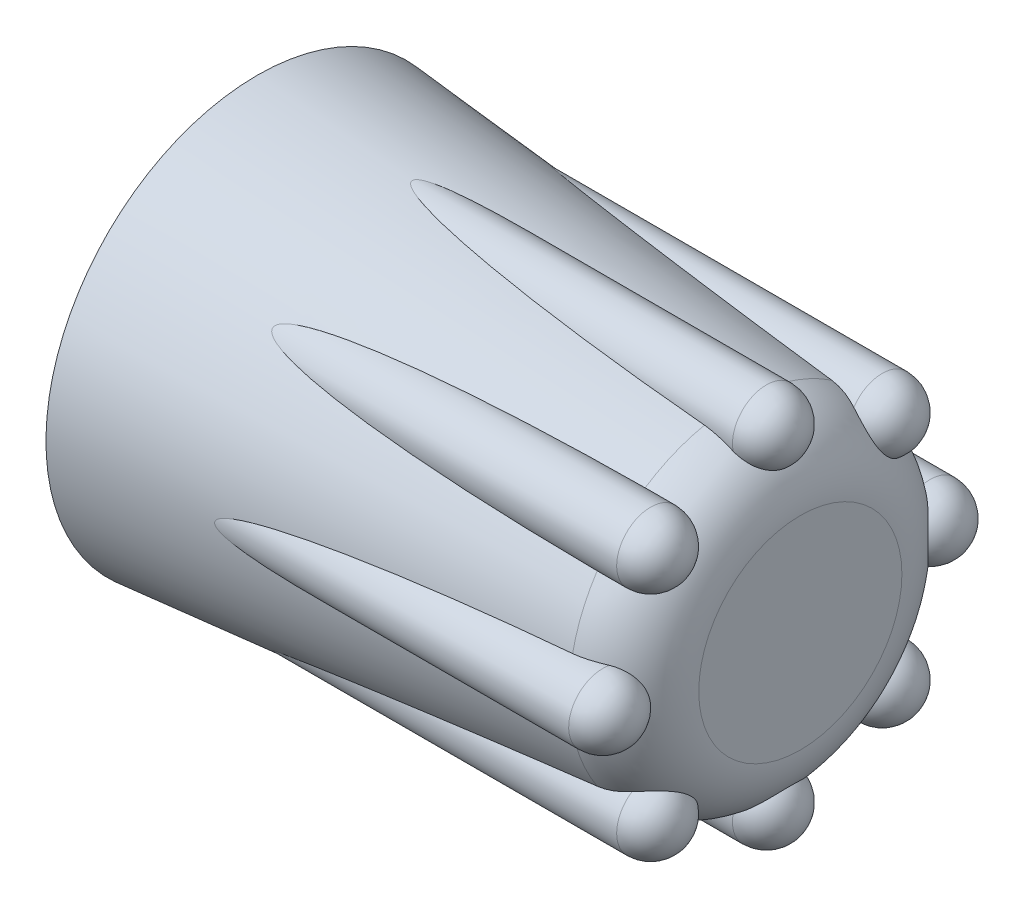
SolidWorks part; units mm, degrees
ref_plane "Front Plane" through (0, 0, 0) normal (0, 0, 1) x (1, 0, 0)
ref_plane "Top Plane" through (0, 0, 0) normal (0, 1, 0) x (1, 0, 0)
ref_plane "Right Plane" through (0, 0, 0) normal (1, 0, 0) x (0, 0, -1)
sketch "Sketch1" plane through (49.6507, 0, 0) normal (1, 0, 0) x (0, 0, -1)
  circle A0 centre (-54.9484, 13.1562) radius 5
  dimension "D1" = 10
extrude "Boss-Extrude1" add sketch "Sketch1" against normal blind 14 draft 5 and the other way blind 2 draft 5
sketch "Sketch2" plane through (35.6507, 0, 0) normal (-1, 0, 0) x (0, 0, 1)
  line L0 (54.9484, 13.1562) -> (58.1732, 13.1562) construction
  line L1 (51.7484, 12.7562) -> (58.1483, 12.7562)
  line L2 (51.7484, 13.5562) -> (58.1483, 13.5562)
  line L3 (54.9484, 13.5562) -> (58.1732, 13.5562) construction
  line L4 (54.9484, 12.7562) -> (58.1732, 12.7562) construction
  arc A1 (51.7484, 12.7562) -> (58.1483, 12.7562) centre (54.9484, 13.1562) ccw
  circle A2 centre (54.9484, 13.1562) radius 3.2248
  arc A3 (58.1483, 13.5562) -> (51.7484, 13.5562) centre (54.9484, 13.1562) ccw
  dimension "D1" = 3
  dimension "D2" = 0.4
  dimension "D3" = 0.4
extrude "Cut-Extrude1" cut sketch "Sketch2" against normal blind 14
fillet "Fillet5" radius 2 1 edges at (51.6507, 17.9812, 54.9484)
sketch "Sketch3" plane through (51.6507, 0, 0) normal (1, 0, 0) x (0, 0, -1)
  circle A0 centre (-54.9484, 17.9812) radius 1
  circle A1 centre (-54.9484, 13.1562) radius 4.825 construction
  circle A2 centre (-51.5366, 16.568) radius 1
  circle A3 centre (-50.1234, 13.1562) radius 1
  circle A4 centre (-51.5366, 9.7444) radius 1
  circle A5 centre (-54.9484, 8.3311) radius 1
  circle A6 centre (-58.3602, 9.7444) radius 1
  circle A7 centre (-59.7734, 13.1562) radius 1
  circle A8 centre (-58.3602, 16.568) radius 1
  dimension "D1" = 2
  dimension "D2" = 8
extrude "Boss-Extrude2" add sketch "Sketch3" along a picked direction on the side against the normal blind 16
fillet "Fillet6" radius 1 8 edges at (51.6507, 18.9812, 54.9484) (51.6507, 17.568, 51.5366) (51.6507, 14.1562, 50.1234) (51.6507, 10.7444, 51.5366) (51.6507, 9.3311, 54.9484) (51.6507, 10.7444, 58.3602) (51.6507, 14.1562, 59.7734) (51.6507, 17.568, 58.3602)
